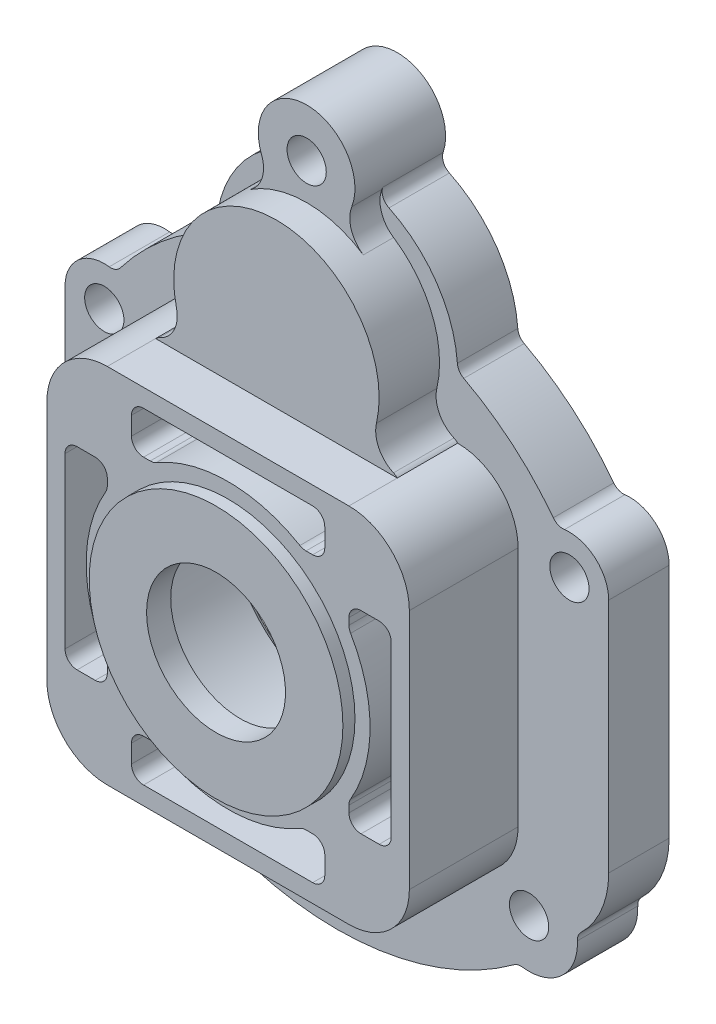
SolidWorks part; units mm, degrees
ref_plane "前视基准面" through (0, 0, 0) normal (0, 0, 1) x (1, 0, 0)
ref_plane "上视基准面" through (0, 0, 0) normal (0, 1, 0) x (1, 0, 0)
ref_plane "右视基准面" through (0, 0, 0) normal (1, 0, 0) x (0, 0, -1)
sketch "草图1" plane through (0, 0, 0) normal (0, 0, 1) x (1, 0, 0)
  line L0 (0, 0) -> (0, -80.9599) construction
  line L1 (-45, 20) -> (-45, -19.1207)
  line L2 (-40.5687, 40) -> (40.5687, 40) construction
  line L3 (-31.8198, -31.8198) -> (0, 0) construction
  line L4 (45, 20) -> (45, -19.1207)
  arc A0 (-45, 20) -> (-36.5793, 26.2098) centre (-38.5, 20) cw
  arc A1 (-36.5793, 26.2098) -> (-19.9976, 40.3125) centre (0, 0) cw
  arc A2 (-19.9976, 40.3125) -> (-6.8115, 58.8043) centre (0, 40) cw
  circle A3 centre (0, 63) radius 8
  circle A4 centre (-31.8198, -31.8198) radius 8
  circle A5 centre (0, 0) radius 45 construction
  arc A6 (-45, -19.1207) -> (-39.7179, -30.5471) centre (-30, -19.1207) ccw
  arc A7 (-30, -39.6101) -> (30, -39.6101) centre (0, 0) ccw
  arc A8 (45, -19.1207) -> (39.7179, -30.5471) centre (30, -19.1207) cw
  circle A9 centre (31.8198, -31.8198) radius 8
  arc A10 (19.9976, 40.3125) -> (6.8115, 58.8043) centre (0, 40) ccw
  arc A11 (36.5793, 26.2098) -> (19.9976, 40.3125) centre (0, 0) ccw
  arc A12 (45, 20) -> (36.5793, 26.2098) centre (38.5, 20) ccw
  point P12 (0, 40)
  point P32 (-39.7179, -30.5471)
  dimension "D2" = 45
  dimension "D4" = 20
  dimension "D5" = 16
  dimension "D7" = 16
  dimension "D8" = 90
  dimension "D10" = 15
  dimension "D11" = 49.6886
  dimension "D12" = 6.5
  dimension "D1" = 45
  dimension "D3" = 40
  dimension "D6" = 23
  dimension "D9" = 45
  dimension "D13" = 20
extrude "凸台-拉伸1" add sketch "草图1" along normal blind 10 contours L4 A12 A11 A10 A3 A2 A1 A0 L1 A6 A4 A7 A9 A8 | A3 | A4 | A9 region at (0, 2.0224, 0) region at (-31.8198, -31.8198, 0) region at (0, 63, 0) region at (31.8198, -31.8198, 0)
fillet "圆角2" radius 2 10 edges at (39.7179, -30.5471, 5) (30, -39.6101, 5) (-30, -39.6101, 5) (-39.7179, -30.5471, 5) (-36.5793, 26.2098, 5) (-19.9976, 40.3125, 5) (-6.8115, 58.8043, 5) (19.9976, 40.3125, 5) (36.5793, 26.2098, 5) (6.8115, 58.8043, 5)
sketch "草图2" plane through (0, 0, 10) normal (0, 0, 1) x (1, 0, 0)
  line L1 (-20, -30) -> (20, -30)
  line L2 (-30, -20) -> (-30, 20)
  line L3 (-20, 30) -> (20, 30)
  line L4 (30, -20) -> (30, 20)
  line L5 (-30, -30) -> (30, 30) construction
  line L6 (-30, 30) -> (30, -30) construction
  arc A0 (20, -30) -> (30, -20) centre (20, -20) ccw
  arc A1 (-30, 20) -> (-20, 30) centre (-20, 20) cw
  arc A2 (-20, -30) -> (-30, -20) centre (-20, -20) cw
  arc A3 (20, 30) -> (30, 20) centre (20, 20) cw
  point P0 (0, 0)
  dimension "D2" = 10
  dimension "D1" = 60
extrude "凸台-拉伸2" add sketch "草图2" along normal blind 18
sketch "草图3" plane through (0, 0, 28) normal (0, 0, 1) x (1, 0, 0)
  circle A0 centre (0, 0) radius 21
  dimension "D1" = 42
extrude "凸台-拉伸3" add sketch "草图3" along normal blind 2
sketch "草图4" plane through (0, 0, 10) normal (0, 0, 1) x (1, 0, 0)
  line L3 (-21.1601, 30) -> (21.3106, 30)
  line L4 (20, 30) -> (-20, 30) construction
  arc A0 (16.5549, 36.1354) -> (-16.5539, 36.131) centre (0, 40) ccw
  arc A1 (19.9495, 41.4205) -> (8.6274, 58.0435) centre (0, 40) ccw construction
  arc A2 (16.5549, 36.1354) -> (21.3106, 30) centre (21.424, 34.9987) ccw
  arc A3 (-16.5539, 36.131) -> (-25.1222, 31.6295) centre (-21.4227, 34.9931) cw
  point P16 (-13.7477, 30)
  dimension "D1" = 34
  dimension "D2" = 5
extrude "凸台-拉伸4" add sketch "草图4" along normal blind 10 contours A0 A3 L3 A2 region at (0.0008, 41.9237, 10)
sketch "草图6" plane through (0, 0, 10) normal (0, 0, 1) x (1, 0, 0)
  line L1 (-21.1601, 30) -> (-20, 30)
  line L2 (-21.1601, 30) -> (-20, 30)
  line L5 (-20, 30) -> (20, 30)
  line L6 (-20, 30) -> (20, 30)
  line L7 (20, 30) -> (21.3106, 30)
  line L8 (20, 30) -> (21.3106, 30)
  arc A0 (7.4702, 60.1371) -> (-7.4702, 60.1371) centre (0, 63) ccw
  arc A1 (7.5922, 60.4783) -> (-7.5922, 60.4783) centre (0, 63) ccw construction
  arc A2 (-9.3802, 54.1779) -> (-16.5539, 36.131) centre (0, 40) ccw
  arc A3 (7.4702, 60.1371) -> (9.3802, 54.1779) centre (12.1391, 58.3478) ccw
  arc A4 (-7.4702, 60.1371) -> (-9.3802, 54.1779) centre (-12.1391, 58.3478) cw
  arc A5 (16.5549, 36.1354) -> (-16.5539, 36.131) centre (0, 40) ccw
  arc A6 (-21.1601, 30) -> (-16.5539, 36.131) centre (-21.4227, 34.9931) ccw
  arc A7 (16.5549, 36.1354) -> (21.3106, 30) centre (21.424, 34.9987) ccw
  arc A8 (16.5549, 36.1354) -> (9.3802, 54.1779) centre (0, 40) ccw
  arc A9 (-21.1601, 30) -> (-16.5539, 36.131) centre (-21.4227, 34.9931) ccw
  arc A10 (16.5549, 36.1354) -> (21.3106, 30) centre (21.424, 34.9987) ccw
  arc A11 (-9.3802, 54.1779) -> (9.3802, 54.1779) centre (0, 40) cw
  point P17 (-4.5083, 56.3913)
  arc M2 (-16.5539, 36.131) -> (16.5549, 36.1354) centre (0, 40) cw
  arc M20 (7.5922, 60.4783) -> (-7.5922, 60.4783) centre (0, 63) ccw
  dimension "D1" = 0
  dimension "D2" = 5
extrude "凸台-拉伸5" add sketch "草图6" along normal blind 5 contours A0 A4 A3 M2 M20 region at (0, 63.061, 10)
sketch "草图7" plane through (0, 0, 15) normal (0, 0, 1) x (1, 0, 0)
  circle A0 centre (0, 63) radius 3.25
  arc A1 (7.4702, 60.1371) -> (-7.4702, 60.1371) centre (0, 63) ccw construction
  dimension "D1" = 6.5
extrude "切除-拉伸1" cut sketch "草图7" against normal through all
sketch "草图8" plane through (0, 0, 10) normal (0, 0, 1) x (1, 0, 0)
  circle A0 centre (-38.5, 20) radius 3.25
  circle A1 centre (-38.5, 20) radius 3.25
  circle A2 centre (38.5, 20) radius 3.25
  circle A3 centre (31.8198, -31.8198) radius 3.25
  arc A4 (-37.678, 26.4478) -> (-45, 20) centre (-38.5, 20) ccw construction
  arc A5 (45, 20) -> (37.678, 26.4478) centre (38.5, 20) ccw construction
  arc A6 (30.7626, -39.7496) -> (39.811, -31.4439) centre (31.8198, -31.8198) ccw construction
  dimension "D1" = 6.5
extrude "切除-拉伸2" cut sketch "草图8" against normal through all contours A2 | A3 | A0
sketch "草图9" plane through (0, 0, 10) normal (0, 0, 1) x (1, 0, 0)
  circle A0 centre (-31.8198, -31.8198) radius 4
  arc A1 (-39.811, -31.4439) -> (-30.7626, -39.7496) centre (-31.8198, -31.8198) ccw construction
  dimension "D1" = 8
extrude "切除-拉伸3" cut sketch "草图9" against normal through all
sketch "草图10" plane through (0, 0, 0) normal (0, 0, -1) x (-1, 0, 0)
  line L2 (0, -1000) -> (0, 49000) construction
  line L3 (41, 11.0139) -> (41, -19.1207)
  line L4 (-41, 20) -> (-41, -19.1207)
  line L5 (41, -19.1207) -> (41, 20)
  line L6 (-41, 11.0139) -> (-41, -19.1207)
  arc A22 (-24.9692, -35.9513) -> (-36.5403, -25.3609) centre (-31.8198, -31.8198) ccw
  arc A23 (-38.8889, 13.0108) -> (-32.3226, 23.2923) centre (-38.5, 20) ccw
  arc A25 (-39.811, -31.4439) -> (-30.7626, -39.7496) centre (-31.8198, -31.8198) ccw construction
  arc A26 (-37.678, 26.4478) -> (-45, 20) centre (-38.5, 20) ccw construction
  arc A28 (-6.902, 54.4348) -> (6.902, 54.4348) centre (0, 40) cw
  arc A29 (-24.9692, -35.9513) -> (-24.3212, -38.6772) centre (-23.2565, -36.9842) ccw
  arc A30 (-36.5403, -25.3609) -> (-39.4361, -24.7741) centre (-37.7204, -23.7462) cw
  arc A31 (-38.8889, 13.0108) -> (-41, 11.0139) centre (-39, 11.0139) ccw
  arc A32 (-32.3226, 23.2923) -> (-32.1246, 25.4757) centre (-30.5576, 24.2329) cw
  arc A33 (19.143, 36.2566) -> (32.1246, 25.4757) centre (0, 0) cw
  arc A34 (19.143, 36.2566) -> (15.9596, 41.1364) centre (21.9444, 41.5625) cw
  arc A35 (6.902, 54.4348) -> (15.9596, 41.1364) centre (0, 40) cw
  arc A36 (41, -19.1207) -> (39.4361, -24.7741) centre (30, -19.1207) cw
  arc A37 (32.3226, 23.2923) -> (32.1246, 25.4757) centre (30.5576, 24.2329) ccw
  arc A38 (38.8889, 13.0108) -> (41, 11.0139) centre (39, 11.0139) cw
  arc A39 (36.5403, -25.3609) -> (39.4361, -24.7741) centre (37.7204, -23.7462) ccw
  arc A40 (24.9692, -35.9513) -> (24.3212, -38.6772) centre (23.2565, -36.9842) cw
  arc A41 (38.8889, 13.0108) -> (32.3226, 23.2923) centre (38.5, 20) cw
  arc A42 (24.9692, -35.9513) -> (36.5403, -25.3609) centre (31.8198, -31.8198) cw
  arc A44 (-41, -19.1207) -> (-37.641, -27.0337) centre (-30, -19.1207) ccw
  arc A45 (-35.8154, -31.6319) -> (-37.641, -27.0337) centre (-41.8088, -31.3499) ccw
  arc A46 (-35.8154, -31.6319) -> (-31.2912, -35.7847) centre (-31.8198, -31.8198) ccw
  arc A47 (-26.958, -36.8878) -> (-31.2912, -35.7847) centre (-30.4983, -41.7321) ccw
  arc A48 (-26.958, -36.8878) -> (26.958, -36.8878) centre (0, 0) ccw
  arc A49 (31.2912, -35.7847) -> (26.958, -36.8878) centre (30.4983, -41.7321) ccw
  arc A50 (31.2912, -35.7847) -> (35.8154, -31.6319) centre (31.8198, -31.8198) ccw
  arc A51 (37.641, -27.0337) -> (35.8154, -31.6319) centre (41.8088, -31.3499) ccw
  arc A52 (37.641, -27.0337) -> (41, -19.1207) centre (30, -19.1207) ccw
  arc A53 (41, 20) -> (38.1838, 22.4799) centre (38.5, 20) ccw
  arc A54 (32.6474, 24.8022) -> (38.1838, 22.4799) centre (37.4251, 28.4318) ccw
  arc A55 (32.6474, 24.8022) -> (19.143, 36.2566) centre (0, 0) ccw
  arc A56 (15.9596, 41.1364) -> (19.143, 36.2566) centre (21.9444, 41.5625) ccw
  arc A57 (15.9596, 41.1364) -> (6.902, 54.4348) centre (0, 40) ccw
  arc A58 (3.7961, 61.7391) -> (6.902, 54.4348) centre (9.4902, 59.8478) ccw
  arc A59 (3.7961, 61.7391) -> (-3.7961, 61.7391) centre (0, 63) ccw
  arc A60 (-6.902, 54.4348) -> (-3.7961, 61.7391) centre (-9.4902, 59.8478) ccw
  arc A61 (-6.902, 54.4348) -> (-15.9596, 41.1364) centre (0, 40) ccw
  arc A62 (-19.143, 36.2566) -> (-15.9596, 41.1364) centre (-21.9444, 41.5625) ccw
  arc A63 (-19.143, 36.2566) -> (-32.6474, 24.8022) centre (0, 0) ccw
  arc A64 (-38.1838, 22.4799) -> (-32.6474, 24.8022) centre (-37.4251, 28.4318) ccw
  arc A65 (-38.1838, 22.4799) -> (-41, 20) centre (-38.5, 20) ccw
  arc A66 (-41, -19.1207) -> (-39.4361, -24.7741) centre (-30, -19.1207) ccw
  arc A70 (-24.3212, -38.6772) -> (24.3212, -38.6772) centre (0, 0) ccw
  arc A83 (-6.902, 54.4348) -> (-15.9596, 41.1364) centre (0, 40) ccw
  arc A84 (-19.143, 36.2566) -> (-15.9596, 41.1364) centre (-21.9444, 41.5625) ccw
  arc A85 (-19.143, 36.2566) -> (-32.1246, 25.4757) centre (0, 0) ccw
  dimension "D2" = 7
  dimension "D3" = 2
  dimension "D1" = 4
extrude "切除-拉伸5" cut sketch "草图10" against normal blind 6.5 contours A70 L2 A28 A83 A84 A85 A32 A23 A31 L6 A66 A30 A22 A29 | L2 A70 A40 A42 A39 A36 L3 A38 A41 A37 A33 A34 A35 A28 region at (16.6516, 1.2328, 0) region at (-16.6516, 1.2328, 0)
sketch "草图11" plane through (0, 0, 6.5) normal (0, 0, -1) x (-1, 0, 0)
  circle A0 centre (0, 40) radius 13
  arc A1 (15.9596, 41.1364) -> (-15.9596, 41.1364) centre (0, 40) ccw construction
  dimension "D1" = 26
extrude "切除-拉伸6" cut sketch "草图11" against normal blind 9
sketch "草图12" plane through (0, 0, 15.5) normal (0, 0, -1) x (-1, 0, 0)
  circle A0 centre (0, 40) radius 11.8
  circle A1 centre (0, 40) radius 13 construction
  dimension "D1" = 23.6
extrude "切除-拉伸7" cut sketch "草图12" against normal blind 0.5
chamfer "倒角1" distance 1 angle 45 1 edges at (-13, 40, 6.5)
fillet "圆角3" radius 2 2 edges at (21.3106, 30, 15) (-21.1601, 30, 15)
sketch "草图13" plane through (0, 0, 30) normal (0, 0, -1) x (-1, 0, 0)
  circle A0 centre (0, 0) radius 21
  dimension "D1" = 42
extrude "切除-拉伸8" cut sketch "草图13" along normal through all from offset 4
chamfer "倒角2" distance 1 angle 45 1 edges at (-21, 0, 6.5)
sketch "草图14" plane through (0, 0, 26) normal (0, 0, -1) x (-1, 0, 0)
  circle A0 centre (0, 0) radius 11.5
  dimension "D1" = 23
extrude "切除-拉伸9" cut sketch "草图14" against normal through all
sketch "草图15" plane through (0, 0, 6.5) normal (0, 0, -1) x (-1, 0, 0)
  line L0 (12.8938, 20) -> (14, 20)
  line L1 (-14, 27) -> (-6, 27)
  line L2 (-16, 25) -> (-16, 22)
  line L3 (-14, 20) -> (-12.8938, 20)
  line L4 (16, 25) -> (16, 22)
  line L5 (-4, 25) -> (-4, 24.7841)
  line L6 (0, 0) -> (0, 7.261) construction
  line L7 (4, 25) -> (4, 24.7841)
  line L8 (6, 27) -> (14, 27)
  arc A1 (11.8825, 20.2745) -> (5.5294, 22.8402) centre (0, 0) ccw
  arc A2 (-5.5294, 22.8402) -> (-11.8825, 20.2745) centre (0, 0) ccw
  arc A3 (4, 24.7841) -> (5.5294, 22.8402) centre (6, 24.7841) ccw
  arc A4 (4, 25) -> (6, 27) centre (6, 25) cw
  arc A5 (11.8825, 20.2745) -> (12.8938, 20) centre (12.8938, 22) ccw
  arc A6 (14, 27) -> (16, 25) centre (14, 25) cw
  arc A7 (14, 20) -> (16, 22) centre (14, 22) ccw
  arc A8 (-4, 24.7841) -> (-5.5294, 22.8402) centre (-6, 24.7841) cw
  arc A9 (-4, 25) -> (-6, 27) centre (-6, 25) ccw
  arc A10 (-16, 22) -> (-14, 20) centre (-14, 22) ccw
  arc A11 (-14, 27) -> (-16, 25) centre (-14, 25) ccw
  arc A12 (-11.8825, 20.2745) -> (-12.8938, 20) centre (-12.8938, 22) cw
  point P13 (4, 24.892)
  point P16 (4, 23.1571)
  point P19 (4, 27)
  point P22 (12.339, 20)
  point P27 (16, 20)
  point P30 (-4, 23.1571)
  point P33 (-4, 27)
  point P36 (-16, 20)
  point P39 (-16, 27)
  dimension "D4" = 47
  dimension "D6" = 2
  dimension "D1" = 7
  dimension "D2" = 32
  dimension "D3" = 27
  dimension "D5" = 8
extrude "切除-拉伸10" cut sketch "草图15" against normal blind 8
pattern_circular "阵列(圆周)1" count 4 over 360 about axis through (0, 0, 6.5) along (0, 0, 1) of "切除-拉伸10"
sketch "草图16" plane through (0, 0, 28) normal (0, 0, 1) x (1, 0, 0)
  line L0 (14, 27) -> (6, 27) construction
  line L1 (-6, 27) -> (-14, 27) construction
  line L2 (14, 27) -> (6, 27)
  line L3 (-6, 27) -> (-14, 27)
  line L4 (14, 20) -> (12.8938, 20) construction
  line L5 (-16, 25) -> (-16, 22) construction
  line L6 (-12.8938, 20) -> (-14, 20) construction
  line L7 (16, 25) -> (16, 22) construction
  line L8 (14, 20) -> (12.8938, 20)
  line L9 (16, 25) -> (16, 22)
  line L10 (-12.8938, 20) -> (-14, 20)
  line L11 (-16, 25) -> (-16, 22)
  line L12 (-6, 27) -> (6, 27)
  arc A0 (-5.5294, 22.8402) -> (-11.8825, 20.2745) centre (0, 0) ccw construction
  arc A1 (-16, 22) -> (-14, 20) centre (-14, 22) ccw construction
  arc A2 (-12.8938, 20) -> (-11.8825, 20.2745) centre (-12.8938, 22) ccw construction
  arc A3 (-14, 27) -> (-16, 25) centre (-14, 25) ccw construction
  arc A4 (11.8825, 20.2745) -> (5.5294, 22.8402) centre (0, 0) ccw construction
  arc A5 (11.8825, 20.2745) -> (12.8938, 20) centre (12.8938, 22) ccw construction
  arc A6 (14, 20) -> (16, 22) centre (14, 22) ccw construction
  arc A7 (16, 25) -> (14, 27) centre (14, 25) ccw construction
  arc A8 (16, 25) -> (14, 27) centre (14, 25) ccw
  arc A9 (14, 20) -> (16, 22) centre (14, 22) ccw
  arc A10 (11.8825, 20.2745) -> (12.8938, 20) centre (12.8938, 22) ccw
  arc A11 (11.8825, 20.2745) -> (5.5294, 22.8402) centre (0, 0) ccw
  arc A12 (-14, 27) -> (-16, 25) centre (-14, 25) ccw
  arc A13 (-12.8938, 20) -> (-11.8825, 20.2745) centre (-12.8938, 22) ccw
  arc A14 (-16, 22) -> (-14, 20) centre (-14, 22) ccw
  arc A15 (-5.5294, 22.8402) -> (-11.8825, 20.2745) centre (0, 0) ccw
  arc A16 (-5.5294, 22.8402) -> (5.5294, 22.8402) centre (0, 0) cw
extrude "切除-拉伸11" cut sketch "草图16" against normal blind 8
pattern_circular "阵列(圆周)2" count 4 over 360 about axis through (0, 0, 30) along (0, 0, -1) of "切除-拉伸11"
